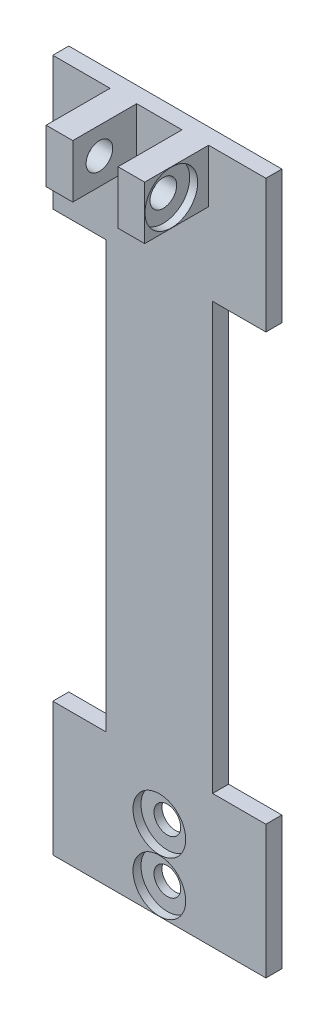
SolidWorks part; units mm, degrees
ref_plane "Front Plane" through (0, 0, 0) normal (0, 0, 1) x (1, 0, 0)
ref_plane "Top Plane" through (0, 0, 0) normal (0, 1, 0) x (1, 0, 0)
ref_plane "Right Plane" through (0, 0, 0) normal (1, 0, 0) x (0, 0, -1)
sketch "Sketch1" plane through (0, 0, 0) normal (0, 0, 1) x (1, 0, 0)
  line L0 (-14.0259, 115.3035) -> (-14.0259, -14.6965) construction
  line L1 (-34.0259, 115.3035) -> (5.9741, 115.3035)
  line L2 (-34.0259, 115.3035) -> (-34.0259, -14.6965)
  line L3 (-34.0259, -14.6965) -> (5.9741, -14.6965)
  line L4 (5.9741, 115.3035) -> (5.9741, -14.6965)
  line L5 (-24.0259, 50.3035) -> (-34.0259, 50.3035) construction
  line L6 (-34.0259, 90.3035) -> (-24.0259, 90.3035)
  line L7 (-34.0259, 90.3035) -> (-34.0259, 10.3035)
  line L8 (-34.0259, 10.3035) -> (-24.0259, 10.3035)
  line L9 (-24.0259, 90.3035) -> (-24.0259, 10.3035)
  line L10 (5.9741, 50.3035) -> (-34.0259, 50.3035) construction
  line L11 (5.9741, 90.3035) -> (-4.0259, 90.3035)
  line L12 (-4.0259, 90.3035) -> (-4.0259, 10.3035)
  line L13 (5.9741, 10.3035) -> (-4.0259, 10.3035)
  line L14 (-14.0259, 105.3035) -> (-14.0259, 115.3035) construction
  line L15 (-18.2759, 115.3035) -> (-9.7759, 115.3035)
  line L16 (-18.2759, 115.3035) -> (-18.2759, 105.3035)
  line L17 (-18.2759, 105.3035) -> (-9.7759, 105.3035)
  line L18 (-9.7759, 115.3035) -> (-9.7759, 105.3035)
  line L20 (-18.2759, 105.3035) -> (-23.2759, 105.3035)
  line L21 (-18.2759, 105.3035) -> (-18.2759, 115.3035)
  line L22 (-18.2759, 115.3035) -> (-23.2759, 115.3035)
  line L23 (-23.2759, 105.3035) -> (-23.2759, 115.3035)
  line L24 (-9.7759, 105.3035) -> (-4.7759, 105.3035)
  line L25 (-9.7759, 105.3035) -> (-9.7759, 115.3035)
  line L26 (-9.7759, 115.3035) -> (-4.7759, 115.3035)
  line L27 (-4.7759, 105.3035) -> (-4.7759, 115.3035)
  circle A0 centre (-14.0259, -9.6965) radius 2.5
  circle A1 centre (-14.0259, 0.3035) radius 2.5
  circle A2 centre (-14.0259, 0.3035) radius 4.95
  circle A3 centre (-14.0259, -9.6965) radius 4.95
  dimension "D3" = 5
  dimension "D4" = 5
  dimension "D5" = 9.9
  dimension "D6" = 9.9
  dimension "D1" = 130
  dimension "D2" = 40
  dimension "D7" = 5
  dimension "D8" = 15
  dimension "D9" = 80
  dimension "D10" = 10
  dimension "D11" = 10
  dimension "D12" = 8.5
  dimension "D13" = 5
  dimension "D14" = 5
extrude "Body" add sketch "Sketch1" along normal blind 3 contours L27 L24 L17 L20 L23 L1 L2 L6 L9 L8 L3 L4 L13 L12 L11 A3 A2 | L23 L20 L16 L1 | L18 L1 L16 L17 | L24 L27 L1 L18 region at (-14.0259, 49.4963, 0) region at (-20.7759, 110.3035, 0) region at (-14.0259, 110.3035, 0) region at (-7.2759, 110.3035, 0)
extrude "Mount Insets" add sketch "Sketch1<3>" along normal blind 1.5 contours A2 A1 | A3 A0 region at (-18.8359, 0.3035, 0) region at (-18.8359, -9.6965, 0)
sketch "Sketch1<3>" plane through (0, 0, 0) normal (0, 0, 1) x (1, 0, 0) same geometry as "Sketch1"
extrude "Hinge" add sketch "Sketch1<5>" along normal blind 15 contours L24 L27 L1 L18 | L20 L23 L22 L21 region at (-7.2759, 110.3035, 0)
sketch "Sketch1<5>" plane through (0, 0, 0) normal (0, 0, 1) x (1, 0, 0) same geometry as "Sketch1"
sketch "Sketch2" plane through (-4.7759, 0, 0) normal (1, 0, 0) x (0, 0, -1)
  line L0 (-15, 110.3035) -> (-3, 110.3035) construction
  line L1 (-15, 105.3035) -> (-15, 115.3035) construction
  line L2 (-3, 115.3035) -> (-3, 105.3035) construction
  line L3 (-10, 115.3035) -> (-10, 105.3035) construction
  line L4 (-15, 115.3035) -> (-3, 115.3035) construction
  line L5 (-15, 105.3035) -> (-3, 105.3035) construction
  circle A0 centre (-10, 110.3035) radius 2.5
  circle A1 centre (-10, 110.3035) radius 4.95
  dimension "D2" = 5
  dimension "D3" = 9.9
  dimension "D1" = 5
extrude "Hinge Inset" cut sketch "Sketch2" against normal blind 1.5
extrude "Hinge Inset2" cut sketch "Sketch2<2>" along normal blind 1.5 from surface starting at face at (-23.2759, 110.3035, 9)
sketch "Sketch2<2>" plane through (-4.7759, 0, 0) normal (1, 0, 0) x (0, 0, -1) same geometry as "Sketch2"
extrude "Hinge Screwhole" cut sketch "Sketch2<3>" against normal through all contours A0 region at (-4.7759, 110.3035, 10)
sketch "Sketch2<3>" plane through (-4.7759, 0, 0) normal (1, 0, 0) x (0, 0, -1) same geometry as "Sketch2"
